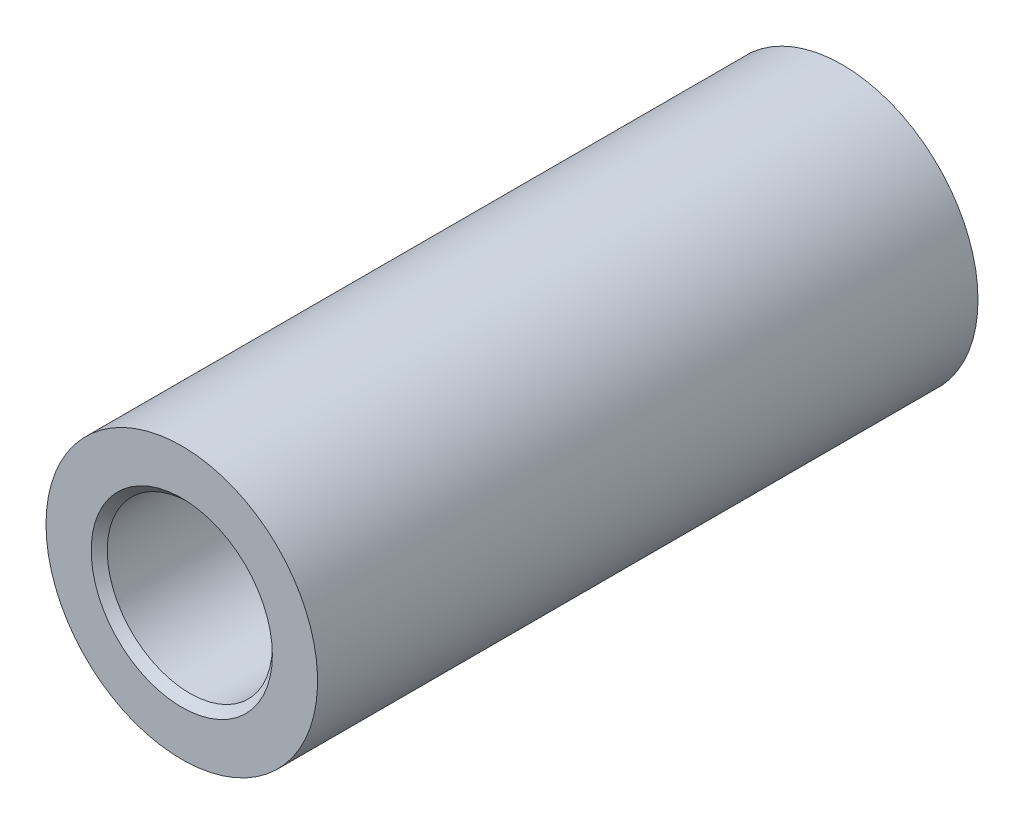
SolidWorks part; units mm, degrees
ref_plane "Front Plane" through (0, 0, 0) normal (0, 0, 1) x (1, 0, 0)
ref_plane "Top Plane" through (0, 0, 0) normal (0, 1, 0) x (1, 0, 0)
ref_plane "Right Plane" through (0, 0, 0) normal (1, 0, 0) x (0, 0, -1)
sketch "Sketch1" plane through (0, 0, 0) normal (0, 0, 1) x (1, 0, 0)
  circle A0 centre (0, 0) radius 9.525 construction
  circle A1 centre (0, 0) radius 4.826 construction
  point P4 (0, 9.525)
  dimension "ID" = 9.652
  dimension "OD" = 19.05
sketch "Sketch2" plane through (0, 0, 0) normal (1, 0, 0) x (0, 0, -1)
  line L0 (-25.4, 9.525) -> (25.4, 9.525) construction
  dimension "Length" = 50.8
sketch "Sketch3" plane through (0, 0, 0) normal (0, 0, 1) x (1, 0, 0)
  circle A0 centre (0, 0) radius 4.826 construction
  circle A1 centre (0, 0) radius 9.525 construction
  circle A2 centre (0, 0) radius 4.826
  circle A3 centre (0, 0) radius 9.525
extrude "Boss-Extrude1" add sketch "Sketch3" against normal up to vertex (25.4 mm away) and the other way up to vertex (25.4 mm away) up to point (0, 9.525, -25.4) other way up to point (0, 9.525, 25.4)
chamfer "Chamfer1" distance 0.4699 angle 45 4 edges at (9.525, 0, 25.4) (9.525, 0, -25.4) (4.826, 0, 25.4) (4.826, 0, -25.4)
sketch "Sketch4" plane through (0, 0, -25.4) normal (0, 0, -1) x (-1, 0, 0)
  circle A0 centre (0, 0) radius 14.7646
extrude "Cut-Extrude1" cut sketch "Sketch4" against normal offset from surface (12.192 mm away) 38.608 up to face at (9.0551, 0, 25.4)
sketch "Sketch5" plane through (0, 0, -13.208) normal (0, 0, -1) x (-1, 0, 0)
  circle A0 centre (0, 0) radius 7.9375
  circle A1 centre (0, 0) radius 9.525 construction
  circle A2 centre (0, 0) radius 9.525
  circle M1 centre (0, 0) radius 9.525
  dimension "D1" = 15.875
extrude "Cut-Extrude2" cut sketch "Sketch5" against normal through all both and the other way through all contours A0 M1 region at (9.2556, 0, -13.208)
equation "\"D1@Chamfer1\"=(\"OD@Sketch1\"-\"ID@Sketch1\")*0.05"
